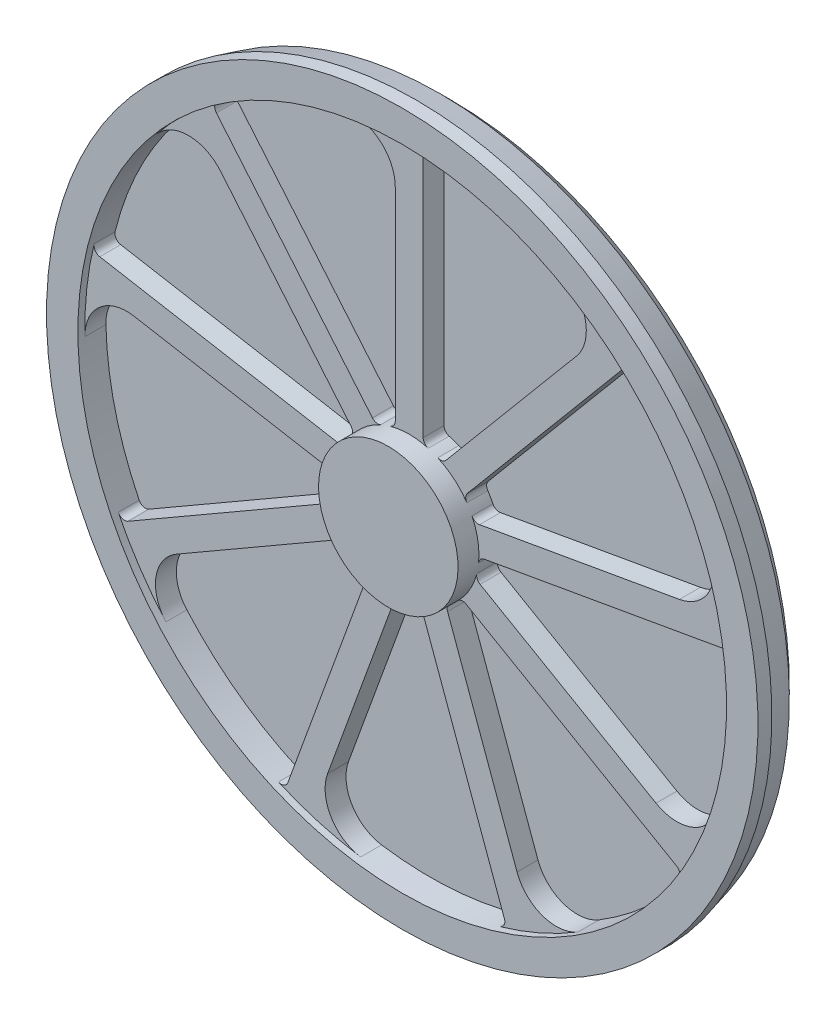
SolidWorks part; units mm, degrees
material "1060 Alloy"
ref_plane "Front Plane" through (0, 0, 0) normal (0, 0, 1) x (1, 0, 0)
ref_plane "Top Plane" through (0, 0, 0) normal (0, 1, 0) x (1, 0, 0)
ref_plane "Right Plane" through (0, 0, 0) normal (1, 0, 0) x (0, 0, -1)
sketch "Sketch1" plane through (0, 0, 0) normal (1, 0, 0) x (0, 0, -1)
  line L0 (0, 0) -> (0, 249.5455) construction
  line L1 (0, 0) -> (0, 485)
  line L2 (0, 0) -> (-30, 0)
  line L3 (-30, 100) -> (-30, 465)
  line L4 (-30, 465) -> (-70, 465)
  line L5 (-70, 465) -> (-70, 510)
  line L6 (-70, 510) -> (-50, 510)
  line L7 (-50, 510) -> (-15.8494, 500.8494)
  line L8 (-30, 0) -> (-90, 0)
  line L9 (-15.8494, 500.8494) -> (0, 485)
  line L10 (-30, 100) -> (-90, 100)
  line L11 (-90, 0) -> (-90, 100)
  line L12 (0, 0) -> (-186.6541, 0) construction
  dimension "D1" = 45
  dimension "D2" = 20
  dimension "D3" = 30
  dimension "D4" = 90
  dimension "D5" = 200
  dimension "D6" = 70
  dimension "D7" = 970
  dimension "D8" = 15
  dimension "D9" = 45
  dimension "D10" = 1020
revolve "Revolve1" add sketch "Sketch1" angle 360 about L12
sketch "Sketch2" plane through (0, 0, 30) normal (0, 0, 1) x (1, 0, 0)
  line L0 (-20, 464.5697) -> (-20, 97.9796)
  line L1 (20, 464.5697) -> (20, 97.9796)
  line L2 (0, 0) -> (0, 640.2584) construction
  circle A0 centre (0, 0) radius 465 construction
  circle A1 centre (0, 0) radius 100 construction
  arc A2 (20, 464.5697) -> (-20, 464.5697) centre (0, 0) ccw
  arc A3 (20, 97.9796) -> (-20, 97.9796) centre (0, 0) ccw
  dimension "D1" = 40
extrude "Boss-Extrude1" add sketch "Sketch2" along normal blind 30
fillet "Fillet1" radius 60 1 edges at (-20, 464.5697, 45)
fillet "Fillet2" radius 10 3 edges at (-20, 97.9796, 45) (20, 97.9796, 45) (20, 464.5697, 45)
pattern_circular "CirPattern1" count 9 over 360 about axis through (0, 0, 70) along (0, 0, -1) of "Boss-Extrude1", "Fillet1", "Fillet2"
